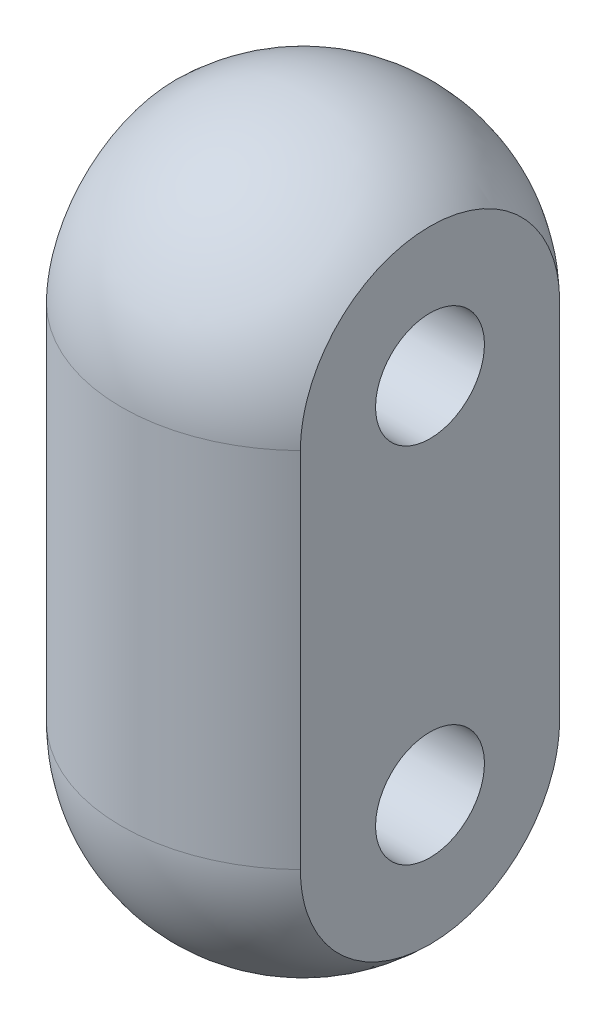
SolidWorks part; units mm, degrees
material "1060 合金"
ref_plane "前视基准面" through (0, 0, 0) normal (0, 0, 1) x (1, 0, 0)
ref_plane "上视基准面" through (0, 0, 0) normal (0, 1, 0) x (1, 0, 0)
ref_plane "右视基准面" through (0, 0, 0) normal (1, 0, 0) x (0, 0, -1)
sketch "草图1" plane through (0, 0, 0) normal (0, 1, 0) x (1, 0, 0)
  circle A0 centre (0, 0) radius 25
  dimension "D1" = 50
extrude "拉伸1" add sketch "草图1" along normal blind 100
fillet "圆角1" radius 25 2 edges at (0, 0, 25) (0, 100, 25)
sketch "草图2" plane through (0, 0, 0) normal (0, 0, 1) x (1, 0, 0)
  line L1 (-17.5, 100) -> (17.5, 100)
  line L2 (-17.5, 100) -> (-17.5, 0)
  line L3 (-17.5, 0) -> (17.5, 0)
  line L4 (17.5, 100) -> (17.5, 0)
  dimension "D1" = 17.5
  dimension "D2" = 100
extrude "拉伸2" cut sketch "草图2" against normal blind 200 and the other way blind 200 flip side to cut
sketch "草图3" plane through (-17.5, 0, 0) normal (-1, 0, 0) x (0, 0, 1)
  line L0 (-17.8536, 25) -> (-17.8536, 75) construction
  circle A0 centre (0, 75) radius 7.5
  circle A1 centre (0, 25) radius 7.5
  dimension "D1" = 15
  dimension "D2" = 17.8536
  dimension "D3" = 50
extrude "拉伸3" cut sketch "草图3" against normal through all
